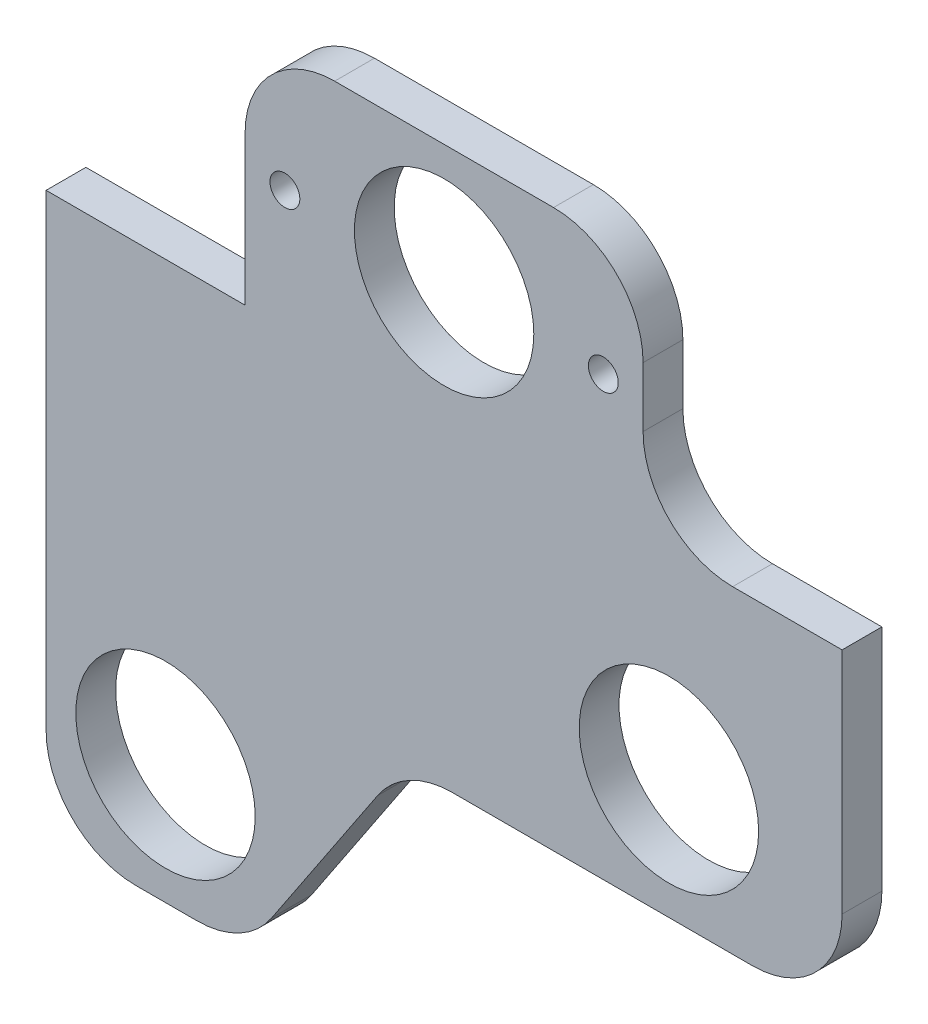
SolidWorks part; units mm, degrees
material "6063-T1"
ref_plane "Front Plane" through (0, 0, 0) normal (0, 0, 1) x (1, 0, 0)
ref_plane "Top Plane" through (0, 0, 0) normal (0, 1, 0) x (1, 0, 0)
ref_plane "Right Plane" through (0, 0, 0) normal (1, 0, 0) x (0, 0, -1)
sketch "Sketch1" plane through (0, 0, 0) normal (0, 0, 1) x (1, 0, 0)
  line L0 (63.5, -6.35) -> (-6.35, -6.35)
  line L1 (-63.5, 44.45) -> (63.5, 44.45)
  line L2 (-63.5, 44.45) -> (-63.5, -44.45)
  line L3 (-63.5, -44.45) -> (63.5, -44.45)
  line L4 (63.5, 44.45) -> (63.5, -44.45)
  line L5 (-63.5, 44.45) -> (63.5, -44.45) construction
  line L6 (-63.5, -44.45) -> (63.5, 44.45) construction
  line L7 (-6.35, -6.35) -> (-31.75, -44.45)
  circle A0 centre (-44.45, -25.4) radius 14.3129
  circle A1 centre (35.8719, 12.7) radius 14.3129
  point P0 (0, 0)
  dimension "D1" = 28.6258
  dimension "D2" = 28.6258
  dimension "D3" = 88.9
  dimension "D4" = 19.05
  dimension "D5" = 57.15
  dimension "D6" = 88.9
  dimension "D7" = 19.05
  dimension "D8" = 127
  dimension "D9" = 38.1
  dimension "D10" = 31.75
  dimension "D11" = 57.15
extrude "Boss-Extrude1" add sketch "Sketch1" along normal blind 6.35 contours L7 L0 L4 L1 L2 L3 A1 A0 region at (-9.2383, 13.2886, 0)
fillet "Fillet1" radius 14.2875 4 edges at (63.5, -6.35, 3.175) (-6.35, -6.35, 3.175) (-31.75, -44.45, 3.175) (-63.5, -44.45, 3.175)
sketch "Sketch2" plane through (0, 0, 6.35) normal (0, 0, 1) x (1, 0, 0)
  line L0 (-63.5, 44.45) -> (63.5, 44.45) construction
  line L1 (-31.75, 44.45) -> (31.75, 44.45)
  line L2 (-31.75, 44.45) -> (-31.75, 82.55)
  line L3 (-31.75, 82.55) -> (31.75, 82.55)
  line L4 (31.75, 44.45) -> (31.75, 82.55)
  line L5 (-63.5, 44.45) -> (-63.5, -30.1625) construction
  dimension "D1" = 38.1
  dimension "D2" = 31.75
  dimension "D3" = 63.5
extrude "Boss-Extrude2" add sketch "Sketch2" against normal blind 6.35
fillet "Fillet2" radius 14.2875 3 edges at (-31.75, 82.55, 3.175) (31.75, 82.55, 3.175) (31.75, 44.45, 3.175)
sketch "Sketch3" plane through (0, 0, 6.35) normal (0, 0, 1) x (1, 0, 0)
  line L1 (17.4625, 82.55) -> (-17.4625, 82.55) construction
  circle A0 centre (0, 63.5) radius 14.3129
  circle A1 centre (35.8719, 12.7) radius 14.3129 construction
  dimension "D1" = 28.6258
  dimension "D2" = 35.8719
  dimension "D3" = 19.05
extrude "Cut-Extrude1" cut sketch "Sketch3" against normal through all
sketch "Sketch4" plane through (0, 0, 6.35) normal (0, 0, 1) x (1, 0, 0)
  circle A0 centre (-25.4, 63.5) radius 2.3813
  circle A1 centre (25.4, 63.5) radius 2.3813
  circle A2 centre (0, 63.5) radius 14.2875
  circle A3 centre (0, 63.5) radius 25.4 construction
  dimension "D1" = 50.8
  dimension "D2" = 4.7625
  dimension "D3" = 4.7625
extrude "Cut-Extrude2" cut sketch "Sketch4" against normal through all
